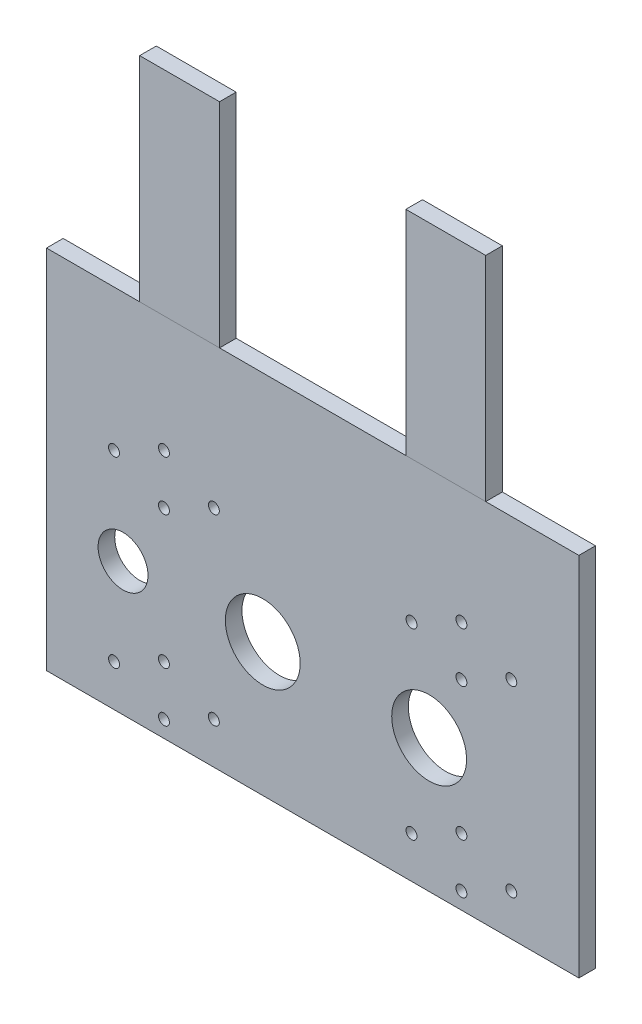
SolidWorks part; units mm, degrees
material "6061 Alloy"
ref_plane "Front Plane" through (0, 0, 0) normal (0, 0, 1) x (1, 0, 0)
ref_plane "Top Plane" through (0, 0, 0) normal (0, 1, 0) x (1, 0, 0)
ref_plane "Right Plane" through (0, 0, 0) normal (1, 0, 0) x (0, 0, -1)
sketch "Sketch1" plane through (0, 0, 0) normal (0, 0, 1) x (1, 0, 0)
  line L1 (0, 0) -> (203.2, 0)
  line L2 (0, 0) -> (0, 101.6)
  line L3 (0, 101.6) -> (203.2, 101.6)
  line L4 (203.2, 0) -> (203.2, 101.6)
  dimension "D1" = 101.6
  dimension "D2" = 203.2
extrude "Boss-Extrude1" add sketch "Sketch1" along normal blind 6.35
sketch "Sketch3" plane through (0, 0, 6.35) normal (0, 0, 1) x (1, 0, 0)
  line L0 (0, 50.8) -> (203.2, 50.8) construction
  line L1 (0, 101.6) -> (0, 0) construction
  line L2 (203.2, 0) -> (203.2, 101.6) construction
  line L3 (101.6, 0) -> (101.6, 101.6) construction
  line L4 (0, 0) -> (203.2, 0) construction
  line L5 (203.2, 101.6) -> (0, 101.6) construction
  circle A0 centre (82.55, 50.8) radius 14.2875
  circle A1 centre (146.05, 50.8) radius 14.2875
  circle A2 centre (29.21, 50.8) radius 9.525
  circle A4 centre (29.21, 50.8) radius 15.24 construction
  circle A5 centre (82.55, 50.8) radius 38.1 construction
  dimension "D1" = 28.575
  dimension "D4" = 19.05
  dimension "D5" = 76.2
  dimension "D6" = 30.48
  dimension "D2" = 63.5
  dimension "D3" = 57.15
extrude "Cut-Extrude2" cut sketch "Sketch3" against normal up to surface (6.35 mm away) up to face at (101.6, 50.8, 0)
sketch "Sketch5" plane through (0, 0, 6.35) normal (0, 0, 1) x (1, 0, 0)
  line L0 (139.319, 85.725) -> (177.419, 85.725) construction
  line L1 (158.369, 95.25) -> (158.369, 76.2) construction
  line L2 (203.2, 0) -> (203.2, 101.6) construction
  line L3 (203.2, 101.6) -> (0, 101.6) construction
  circle A0 centre (139.319, 85.725) radius 2.0828
  circle A1 centre (158.369, 95.25) radius 2.0828
  circle A2 centre (158.369, 76.2) radius 2.0828
  circle A3 centre (177.419, 85.725) radius 2.0828
  point P8 (158.369, 85.725)
  dimension "D5" = 4.1656
  dimension "D1" = 19.05
  dimension "D2" = 38.1
  dimension "D3" = 44.831
  dimension "D4" = 15.875
extrude "Cut-Extrude3" cut sketch "Sketch5" against normal through all
ref_plane "Plane1" through (0, 50.8, 0) normal (0, 1, 0) x (1, 0, 0)
ref_plane "Plane2" through (101.6, 0, 0) normal (1, 0, 0) x (0, 0, -1)
mirror "Mirror1" about plane through (0, 50.8, 0) normal (0, 1, 0) of "Cut-Extrude3"
mirror "Mirror2" about plane through (101.6, 0, 0) normal (1, 0, 0) of "Mirror1"
sketch "Sketch6" plane through (0, 0, 0) normal (0, 0, -1) x (-1, 0, 0)
  line L1 (0, 101.6) -> (-203.2, 101.6)
  line L2 (0, 101.6) -> (0, 139.7)
  line L3 (0, 139.7) -> (-203.2, 139.7)
  line L4 (-203.2, 101.6) -> (-203.2, 139.7)
  line L6 (-203.2, 0) -> (-203.2, 101.6) construction
  dimension "D1" = 38.1
extrude "Boss-Extrude2" add sketch "Sketch6" against normal up to surface (6.35 mm away)
sketch "Sketch8" plane through (0, 139.7, 0) normal (0, 1, 0) x (1, 0, 0)
  line L0 (0, 0) -> (203.2, 0) construction
  line L1 (167.64, 0) -> (137.16, 0)
  line L2 (167.64, 0) -> (167.64, -6.35)
  line L3 (167.64, -6.35) -> (137.16, -6.35)
  line L4 (137.16, 0) -> (137.16, -6.35)
  line L5 (0, -6.35) -> (203.2, -6.35) construction
  line L6 (203.2, -6.35) -> (203.2, 0) construction
  line L7 (101.6, 0) -> (101.6, -6.35) construction
  line L8 (66.04, 0) -> (66.04, -6.35)
  line L9 (35.56, 0) -> (66.04, 0)
  line L10 (35.56, -6.35) -> (66.04, -6.35)
  line L11 (35.56, 0) -> (35.56, -6.35)
  dimension "D1" = 30.48
  dimension "D2" = 35.56
extrude "Boss-Extrude3" add sketch "Sketch8" along normal blind 81.3816 separate body
